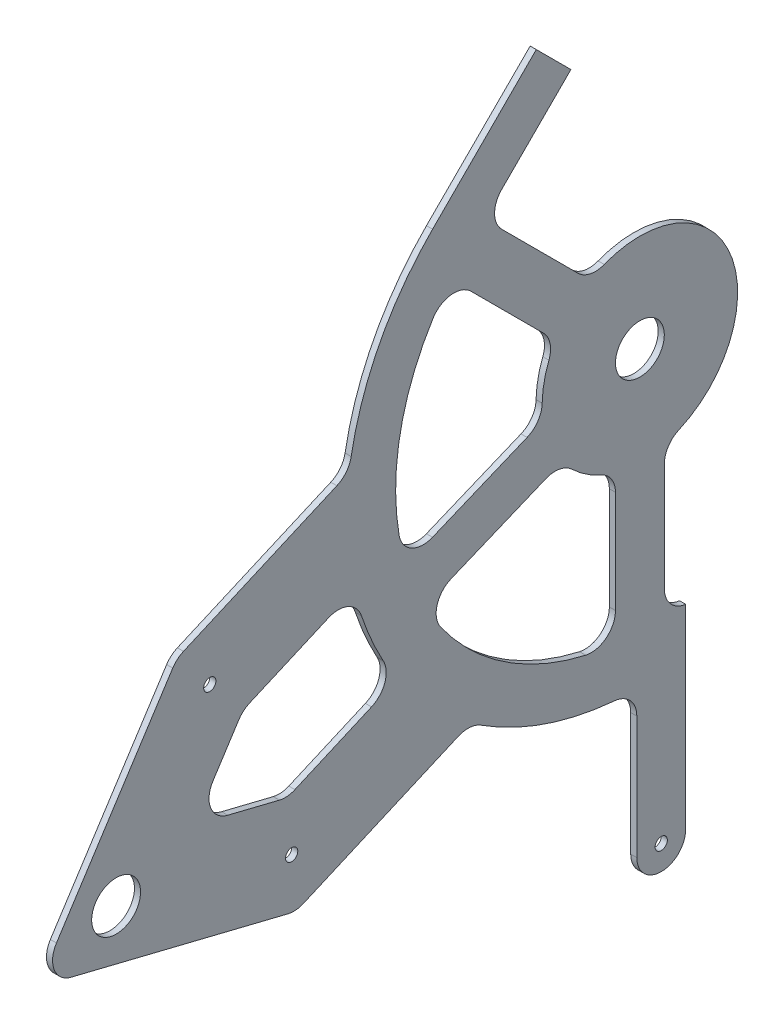
SolidWorks part; units mm, degrees
ref_plane "Front Plane" through (0, 0, 0) normal (0, 0, 1) x (1, 0, 0)
ref_plane "Top Plane" through (0, 0, 0) normal (0, 1, 0) x (1, 0, 0)
ref_plane "Right Plane" through (0, 0, 0) normal (1, 0, 0) x (0, 0, -1)
sketch "Sketch8" plane through (0, 0, 0) normal (1, 0, 0) x (0, 0, -1)
  line L0 (0, 0) -> (-139.7, 0) construction
  circle A1 centre (-272.2355, -114.6296) radius 12.7
  circle A3 centre (-223.5488, -39.2772) radius 3.175
  circle A5 centre (-180.9898, -137.1562) radius 3.175
  circle A7 centre (0, 0) radius 12.7
  circle A9 centre (11.1033, -228.1813) radius 3.175
  circle A10 centre (0, 0) radius 336.7856
  circle A11 centre (0, 0) radius 127
  circle A12 centre (0, 0) radius 152.4
sketch "Sketch9" plane through (0, 0, 0) normal (1, 0, 0) x (0, 0, -1)
  line L0 (0, -126.9544) -> (0, -152.3905)
  line L1 (-89.7703, 89.7703) -> (-107.7564, 107.7564) construction
  line L2 (-98.7633, 98.7633) -> (-44.8818, 152.6449) construction
  line L3 (-107.7564, 107.7564) -> (-53.8406, 161.6722)
  line L4 (-53.8406, 161.6722) -> (-35.8545, 143.6861)
  line L5 (-35.8545, 143.6861) -> (-89.7703, 89.7703)
  arc A0 (-107.7564, 107.7564) -> (0, -152.3905) centre (0, 0) ccw
  arc A1 (-89.7703, 89.7703) -> (0, -126.9544) centre (0, 0) ccw
extrude "Boss-Extrude2" add sketch "Sketch9" along normal blind 3.175
sketch "Sketch11" plane through (0, 0, 0) normal (1, 0, 0) x (0, 0, -1)
  line L0 (0, -152.3905) -> (0, -126.9544) construction
  line L1 (0, -152.3905) -> (0, -126.9544)
  line L2 (0, -126.9544) -> (76.2, -126.9544)
  line L3 (76.2, -126.9544) -> (76.2, -152.3905)
  line L4 (76.2, -152.3905) -> (0, -152.3905)
extrude "Boss-Extrude4" add sketch "Sketch11" along normal blind 3.175
sketch "Sketch12" plane through (0, 0, 0) normal (1, 0, 0) x (0, 0, -1)
  line L0 (11.1033, -228.1813) -> (11.1033, -152.3905) construction
  line L1 (0, -152.3905) -> (76.2, -152.3905) construction
  line L2 (23.8033, -228.1813) -> (23.8033, -152.3905)
  line L3 (-1.5967, -228.1813) -> (-1.5967, -152.3822)
  line L4 (0, -152.3905) -> (23.8033, -152.3905)
  line L5 (-1.5967, -228.1813) -> (-1.5967, -152.3905) construction
  circle A0 centre (11.1033, -228.1813) radius 3.175 construction
  circle A1 centre (11.1033, -228.1813) radius 3.175
  arc A2 (-107.7564, 107.7564) -> (0, -152.3905) centre (0, 0) ccw construction
  arc A3 (-1.5967, -152.3822) -> (0, -152.3905) centre (0, 0) ccw
  arc A4 (23.8033, -228.1813) -> (-1.5717, -227.3844) centre (11.1033, -228.1813) cw
extrude "Boss-Extrude5" add sketch "Sketch12" along normal blind 3.175 contours A4 L2 L4 A3 L3 A1 region at (0, -194.8352, -11.1033)
sketch "Sketch13" plane through (0, 0, 0) normal (1, 0, 0) x (0, 0, -1)
  line L0 (-223.5488, -39.2772) -> (-152.1684, -8.2246) construction
  line L1 (-180.9898, -137.1562) -> (-109.4511, -106.0346) construction
  line L2 (-180.9898, -137.1562) -> (-272.2355, -114.6296) construction
  line L3 (-272.2355, -114.6296) -> (-223.5488, -39.2772) construction
  line L4 (-272.2355, -114.6296) -> (-141.0941, -57.5789) construction
  line L5 (-179.3041, -108.7234) -> (-126.0941, -85.5754)
  line L6 (-187.4143, -109.4075) -> (-214.2907, -102.7723)
  line L7 (-221.9139, -83.5503) -> (-208.4616, -62.7302)
  line L8 (-202.8607, -57.9767) -> (-148.4762, -34.3177)
  line L9 (-174.7967, -162.1614) -> (-88.0105, -124.4067)
  line L10 (-182.9069, -162.8455) -> (-295.6091, -135.0218)
  line L11 (-303.2322, -115.7997) -> (-242.8006, -22.2699)
  line L12 (-237.1998, -17.5164) -> (-151.0792, 19.9487)
  line L13 (-240.7183, -19.0471) -> (-162.301, 15.0669) construction
  line L14 (-178.7361, -163.8752) -> (-99.3186, -129.3261) construction
  line L15 (-206.3792, -59.5074) -> (-142.0359, -31.516) construction
  line L16 (-183.2435, -110.4372) -> (-119.5836, -82.7431) construction
  line L17 (-312.8947, -130.7543) -> (-240.7183, -19.0471) construction
  line L18 (-178.7361, -163.8752) -> (-312.8947, -130.7543) construction
  line L19 (-183.2435, -110.4372) -> (-231.5763, -98.5049) construction
  line L20 (-231.5763, -98.5049) -> (-206.3792, -59.5074) construction
  circle A0 centre (-180.9898, -137.1562) radius 3.175 construction
  circle A1 centre (-272.2355, -114.6296) radius 12.7 construction
  circle A2 centre (-223.5488, -39.2772) radius 3.175 construction
  circle A3 centre (-180.9898, -137.1562) radius 3.175
  circle A4 centre (-272.2355, -114.6296) radius 12.7
  circle A5 centre (-223.5488, -39.2772) radius 3.175
  arc A7 (-107.7564, 107.7564) -> (-1.5967, -152.3822) centre (0, 0) ccw construction
  arc A8 (-107.7564, 107.7564) -> (-1.5967, -152.3822) centre (0, 0) ccw construction
  arc A9 (-151.0792, 19.9487) -> (-148.4762, -34.3177) centre (0, 0) ccw
  arc A10 (-126.0941, -85.5754) -> (-88.0105, -124.4067) centre (0, 0) ccw
  arc A11 (-242.8006, -22.2699) -> (-237.1998, -17.5164) centre (-232.1335, -29.1622) cw
  arc A12 (-174.7967, -162.1614) -> (-182.9069, -162.8455) centre (-179.8629, -150.5157) cw
  arc A13 (-179.3041, -108.7234) -> (-187.4143, -109.4075) centre (-184.3703, -97.0777) cw
  arc A14 (-208.4616, -62.7302) -> (-202.8607, -57.9767) centre (-197.7945, -69.6225) cw
  arc A15 (-295.6091, -135.0218) -> (-303.2322, -115.7997) centre (-292.5651, -122.692) cw
  arc A16 (-214.2907, -102.7723) -> (-221.9139, -83.5503) centre (-211.2468, -90.4425) cw
  dimension "D1" = 12.7
extrude "Boss-Extrude6" add sketch "Sketch13" along normal blind 3.175
fillet "Fillet1" radius 12.7 6 edges at (1.5875, -34.3177, 148.4762) (1.5875, -85.5754, 126.0941) (1.5875, -124.4067, 88.0105) (1.5875, -152.3822, 1.5967) (1.5875, -152.3905, -23.8033) (1.5875, 19.9487, 151.0792)
sketch "Sketch14" plane through (0, 0, 0) normal (1, 0, 0) x (0, 0, -1)
  line L0 (0, 0) -> (-117.2906, -48.5833) construction
  line L1 (0, 0) -> (0, -126.9544) construction
  line L2 (0, 0) -> (-89.7703, 89.7703) construction
  line L3 (-25.8001, 43.7606) -> (-80.79, 98.7506)
  line L4 (76.2, -126.9544) -> (0, -126.9544) construction
  line L5 (12.7, -126.9544) -> (0, -126.9544)
  line L6 (-89.7703, 89.7703) -> (-35.8545, 143.6861) construction
  line L7 (-89.7703, 89.7703) -> (-80.79, 98.7506)
  line L8 (12.7, -49.1869) -> (12.7, -126.9544)
  line L9 (12.7, 0) -> (12.7, -126.9544) construction
  line L10 (-12.7, -49.1869) -> (-12.7, -126.3176)
  line L12 (-40.5827, -30.5563) -> (-111.8421, -60.0729)
  line L14 (-50.3028, -7.0897) -> (-121.5623, -36.6064)
  line L16 (-43.7606, 25.8001) -> (-98.3003, 80.3397)
  line L18 (8.9803, 8.9803) -> (-80.79, 98.7506) construction
  circle A0 centre (0, 0) radius 12.7 construction
  circle A1 centre (0, 0) radius 12.7
  arc A2 (-89.7703, 89.7703) -> (0, -126.9544) centre (0, 0) ccw construction
  arc A3 (-40.5827, -30.5563) -> (-12.7, -49.1869) centre (0, 0) ccw
  arc A4 (12.7, -49.1869) -> (-25.8001, 43.7606) centre (0, 0) ccw
  arc A5 (-43.7606, 25.8001) -> (-50.3028, -7.0897) centre (0, 0) ccw
  arc A6 (-89.7703, 89.7703) -> (-98.3003, 80.3397) centre (0, 0) ccw
  arc A7 (-121.5623, -36.6064) -> (-111.8421, -60.0729) centre (0, 0) ccw
  arc A8 (-12.7, -126.3176) -> (0, -126.9544) centre (0, 0) ccw
extrude "Boss-Extrude7" add sketch "Sketch14" along normal blind 3.175
fillet "Fillet2" radius 12.7 12 edges at (1.5875, -7.0897, 50.3028) (1.5875, 25.8001, 43.7606) (1.5875, 80.3397, 98.3003) (1.5875, -36.6064, 121.5623) (1.5875, -60.0729, 111.8421) (1.5875, -30.5563, 40.5827) (1.5875, -49.1869, 12.7) (1.5875, -126.3176, 12.7) (1.5875, -126.9544, -12.7) (1.5875, -49.1869, -12.7) (1.5875, 43.7606, 25.8001) (1.5875, 98.7506, 80.79)
sketch "Sketch15" plane through (3.175, 0, 0) normal (1, 0, 0) x (0, 0, -1)
  line L0 (23.8033, -165.0905) -> (23.8033, -126.8536)
  line L1 (36.5033, -152.3905) -> (76.2, -152.3905)
  line L2 (76.2, -152.3905) -> (76.2, -126.9544)
  line L3 (76.2, -126.9544) -> (23.8033, -126.8536)
  arc A0 (12.7, -114.2544) -> (25.4, -126.9544) centre (25.4, -114.2544) ccw construction
  arc A1 (23.8033, -165.0905) -> (36.5033, -152.3905) centre (36.5033, -165.0905) cw
extrude "Cut-Extrude1" cut sketch "Sketch15" against normal through all both and the other way through all
